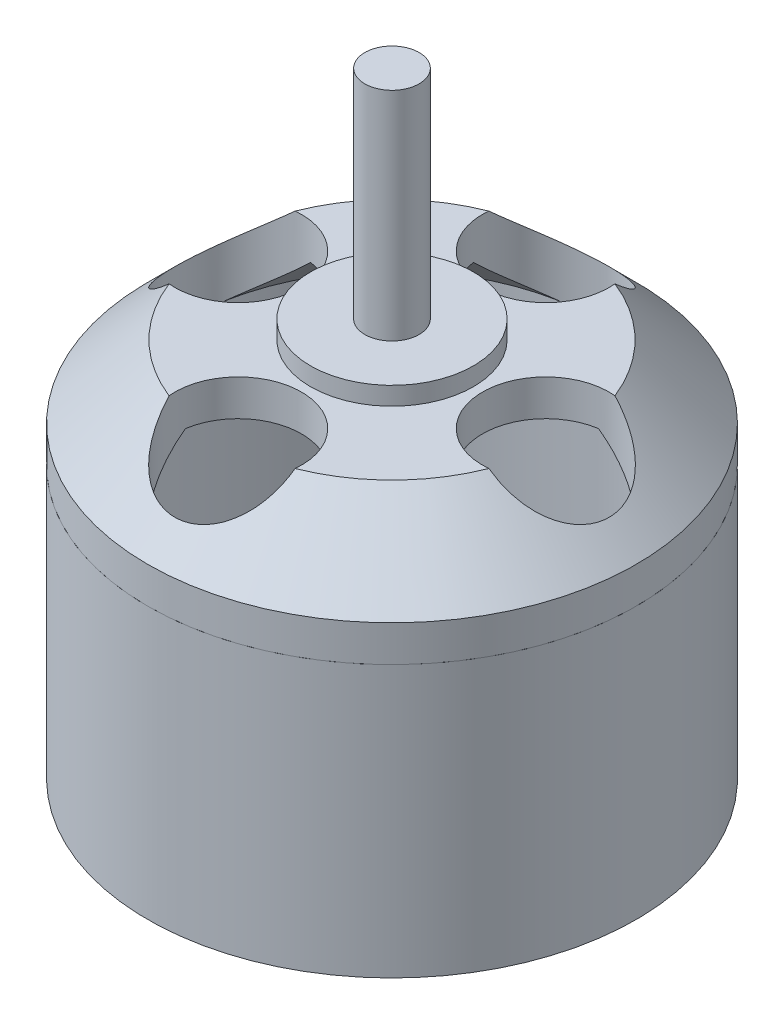
SolidWorks part; units mm, degrees
ref_plane "Ön Düzlem" through (0, 0, 0) normal (0, 0, 1) x (1, 0, 0)
ref_plane "Üst Düzlem" through (0, 0, 0) normal (0, 1, 0) x (1, 0, 0)
ref_plane "Sağ Düzlem" through (0, 0, 0) normal (1, 0, 0) x (0, 0, -1)
sketch "Çizim2" plane through (0, 0, 0) normal (0, 1, 0) x (1, 0, 0)
  circle A0 centre (0, 0) radius 13.5
  dimension "D1" = 27
extrude "Yükseklik-Ekstrüzyon1" add sketch "Çizim2" along normal blind 1
sketch "Çizim3" plane through (0, 1, 0) normal (0, 1, 0) x (1, 0, 0)
  circle A1 centre (0, 0) radius 13.5
  circle A2 centre (0, 0) radius 13.5
  dimension "D1" = 0
extrude "Yükseklik-Ekstrüzyon2" add sketch "Çizim3" along normal blind 5
chamfer "Pah1" distance 4 angle 45 1 edges at (0, 6, 13.5)
shell "İç Boşaltma1" thickness 2 removed face at (0, 0, 13.5)
sketch "Çizim5" plane through (0, 6, 0) normal (0, 1, 0) x (1, 0, 0)
  circle A0 centre (0, -8.5) radius 3.5
  circle A1 centre (-8.5, 0) radius 3.5
  circle A2 centre (0, 8.5) radius 3.5
  circle A3 centre (8.5, 0) radius 3.5
  point P0 (0, 0)
  point P12 (0, 0)
  dimension "D2" = 7
  dimension "D1" = 17
  dimension "D3" = 4
extrude "Kes-Ekstrüzyon1" cut sketch "Çizim5" against normal blind 6
sketch "Çizim6" plane through (0, 0, 0) normal (0, -1, 0) x (1, 0, 0)
  circle A2 centre (0, 0) radius 13.5 construction
  circle A3 centre (0, 0) radius 13.5
  circle A4 centre (0, 0) radius 12.5
  point P1 (1.6678, 2.1985)
  circle M9 centre (0, 0) radius 13.5
  dimension "D1" = 27
  dimension "D2" = 25
sketch "Çizim7" plane through (0, 6, 0) normal (0, 1, 0) x (1, 0, 0)
  circle A0 centre (0, 0) radius 4.5
  dimension "D1" = 9
extrude "Yükseklik-Ekstrüzyon4" add sketch "Çizim7" along normal blind 1
sketch "Çizim8" plane through (0, 7, 0) normal (0, 1, 0) x (1, 0, 0)
  circle A0 centre (0, 0) radius 1.5
  dimension "D1" = 3
extrude "Yükseklik-Ekstrüzyon6" add sketch "Çizim6" along normal blind 15 separate body contours A4 M9
extrude "Yükseklik-Ekstrüzyon7" add sketch "Çizim8" along normal blind 12 and the other way blind 30 separate body
